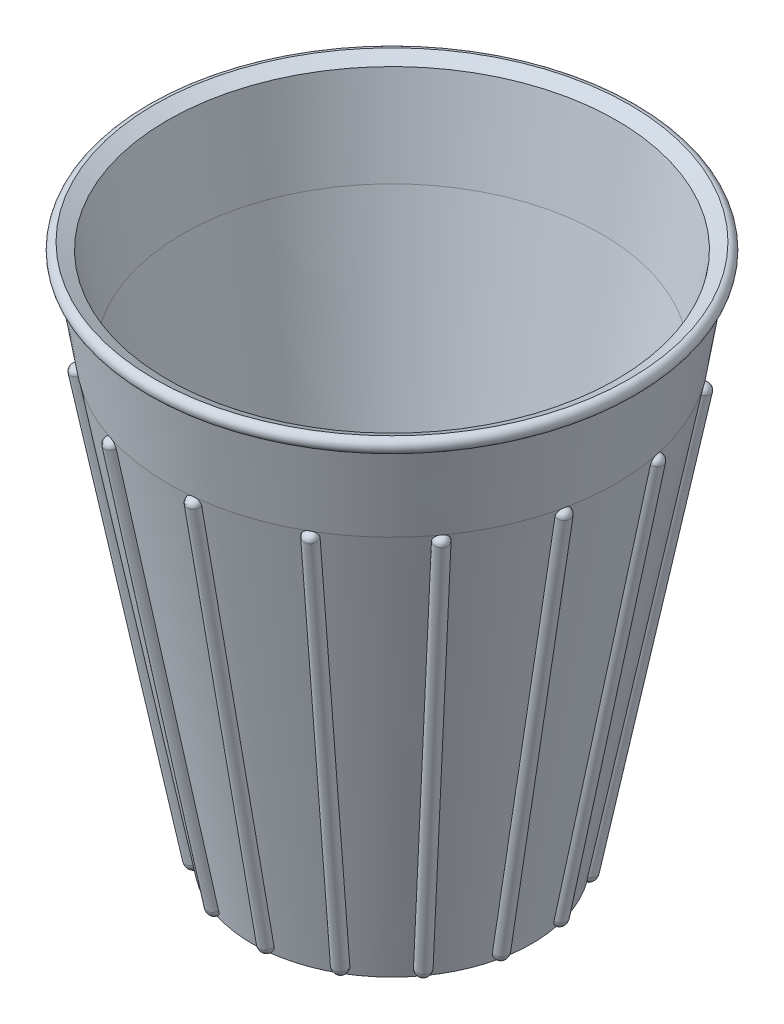
SolidWorks part; units mm, degrees
ref_plane "Front Plane" through (0, 0, 0) normal (0, 0, 1) x (1, 0, 0)
ref_plane "Top Plane" through (0, 0, 0) normal (0, 1, 0) x (1, 0, 0)
ref_plane "Right Plane" through (0, 0, 0) normal (1, 0, 0) x (0, 0, -1)
sketch "Sketch1" plane through (0, 0, 0) normal (0, 0, 1) x (1, 0, 0)
  line L0 (0, 0) -> (0, -77) construction
  line L1 (-20, -77) -> (20, -77) construction
  line L2 (-34, 0) -> (34, 0) construction
  line L3 (-32.1307, -1) -> (-34, 0)
  line L6 (21.5561, -64) -> (20, -77) construction
  line L7 (-12.6, -77) -> (-12.3226, -76.7781)
  line L9 (-34, -2) -> (34, -2) construction
  line L10 (-35, -1) -> (35, -1) construction
  line L11 (-32, -14) -> (32, -14) construction
  line L12 (-34, -2) -> (-32, -14)
  line L15 (34, -2) -> (32, -14) construction
  line L16 (32, -14) -> (27.5, -50.547) construction
  line L17 (27.5, -50.547) -> (23.9354, -64) construction
  line L19 (21.5561, -64) -> (23.9354, -64) construction
  line L22 (0, -74) -> (-18.5355, -74)
  line L27 (-29.964, -14) -> (-32.1307, -1)
  line L28 (-29.964, -14) -> (-18.5355, -74)
  line L29 (-20, -77) -> (-12.6, -77)
  line L30 (-12.6, -76.6) -> (-12.6, -75.2)
  line L31 (-12.6, -75.2) -> (0, -75.2)
  line L32 (0, -75.2) -> (0, -74)
  line L33 (-32, -14) -> (-20, -77)
  line L34 (-12.3851, -76.6) -> (-12.6, -76.6)
  arc A0 (-34, -2) -> (-34, 0) centre (-34, -1) cw
  arc A1 (34, -2) -> (34, 0) centre (34, -1) ccw construction
  arc A2 (-12.3226, -76.7781) -> (-12.3851, -76.6) centre (-12.3851, -76.7) ccw
  point P6 (0, -77)
  point P11 (0, 0)
  point P22 (0, -2)
  point P25 (0, -1)
  point P28 (0, -14)
  point P32 (-12.1, -76.6)
  dimension "D7" = 0.1
  dimension "D1" = 77
  dimension "D2" = 40
  dimension "D3" = 68
  dimension "D4" = 0.5
  dimension "D5" = 2
  dimension "D6" = 0.4
  dimension "D9" = 2
  dimension "D10" = 68
  dimension "D11" = 70
  dimension "D12" = 1
  dimension "D13" = 14
  dimension "D14" = 64
  dimension "D15" = 1.8
  dimension "D20" = 12.6
  dimension "D21" = 3
revolve "Revolve1" add sketch "Sketch1" angle 360 about L0
sketch "Sketch2" plane through (0, 0, 0) normal (0, 0, 1) x (1, 0, 0)
  line L1 (-32, -14) -> (-20, -77)
  line L4 (-32.9713, -8.9005) -> (9322.6341, -49125.8288) construction
  line L5 (-19.1725, -76) -> (-30.7915, -15) construction
  line L6 (-32, -14) -> (-20, -77) construction
  line L7 (-21.2085, -76) -> (-32.8275, -15)
  line L8 (-32, -14) -> (32, -14) construction
  line L11 (-20, -77) -> (-32, -14)
  line L12 (-20, -77) -> (20, -77) construction
  arc A3 (-32.8275, -15) -> (-32, -14) centre (-32, -14.8424) cw
  arc A4 (-21.2085, -76) -> (-20, -77) centre (-20, -75.7698) ccw
  dimension "D3" = 1
  dimension "D1" = 1
  dimension "D4" = 2
  dimension "D5" = 1
  dimension "D6" = 1
  dimension "D7" = 1
revolve "Revolve7" add sketch "Sketch2" angle 360 about L4
pattern_circular "CirPattern1" count 15 over 360 about axis through (0, -14, 0) along (0, 1, 0) of "Revolve7"
